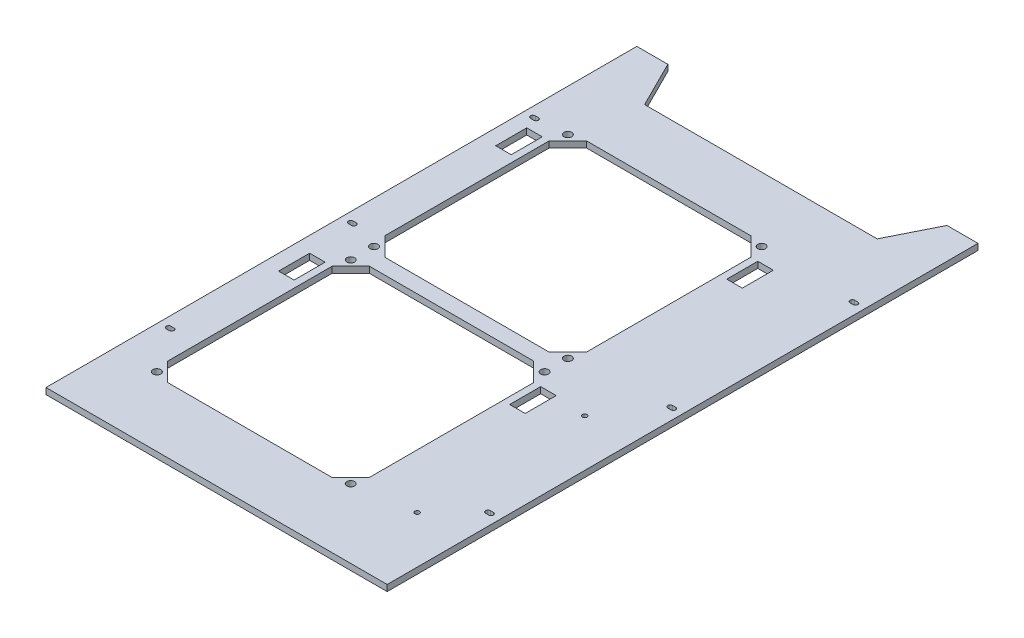
SolidWorks part; units mm, degrees
ref_plane "前基準面" through (0, 0, 0) normal (0, 0, 1) x (1, 0, 0)
ref_plane "上基準面" through (0, 0, 0) normal (0, 1, 0) x (1, 0, 0)
ref_plane "右基準面" through (0, 0, 0) normal (1, 0, 0) x (0, 0, -1)
sketch "草圖1" plane through (0, 0, 0) normal (0, 1, 0) x (1, 0, 0)
  line L1 (-110, 190.5) -> (110, 190.5)
  line L2 (-110, 190.5) -> (-110, -190.5)
  line L3 (-110, -190.5) -> (110, -190.5)
  line L4 (110, 190.5) -> (110, -190.5)
  line L5 (-110, 190.5) -> (110, -190.5) construction
  line L6 (-110, -190.5) -> (110, 190.5) construction
  point P0 (0, 0)
  dimension "D1" = 220
  dimension "D2" = 381
extrude "填料-伸長1" add sketch "草圖1" along normal blind 4
sketch "草圖4" plane through (0, 4, 0) normal (0, 1, 0) x (1, 0, 0)
  line L0 (-110, -190.5) -> (110, -190.5) construction
  line L1 (-103, -117.5) -> (-93, -117.5) construction
  line L2 (-110, 190.5) -> (-110, -190.5) construction
  line L4 (103, -117.5) -> (93, -117.5) construction
  line L5 (103, -117.5) -> (103, 0) construction
  line L6 (110, -190.5) -> (110, 190.5) construction
  line L7 (-103, -117.5) -> (-103, 0) construction
  point P0 (-103, -117.5)
  point P15 (103, -117.5)
  point P21 (93, -117.5)
  point P22 (93, 0)
  point P23 (93, 117.5)
  point P24 (103, 0)
  point P25 (103, 117.5)
  point P26 (-93, -117.5)
  point P27 (-93, 0)
  point P28 (-93, 117.5)
  point P29 (-103, 0)
  point P30 (-103, 117.5)
  dimension "D3" = 2
  dimension "D4" = 3
  dimension "D5" = 7
  dimension "D6" = 10
  dimension "D9" = 3
  dimension "D10" = 10
  dimension "D11" = 7
  dimension "D12" = 117.5
  dimension "D2" = 73
  dimension "D13" = 117.5
  dimension "D7" = 73
  dimension "D8" = 2
hole_wizard "Ø3.0mm 定位孔3" positions "3D草圖6" profile "草圖15" hole size "Ø3.0" standard "GB" end condition through all
sketch3d "3D草圖6"
  point P0 (-103, 4, -117.5)
  point P3 (103, 4, -117.5)
  point P6 (103, 4, 0)
  point P9 (-103, 4, 0)
  point P12 (103, 4, 117.5)
  point P15 (-103, 4, 117.5)
sketch "草圖15" plane through (-103, 4, -117.5) normal (1, 0, 0) x (0, 0, 1)
  line L0 (0, 0) -> (0, 4)
  line L1 (0, 4) -> (1.5, 4)
  line L2 (1.5, 4) -> (1.5, 0)
  line L5 (1.5, 0) -> (0, 0)
  line L11 (0, -6.35) -> (0, 107.95) construction
  dimension "貫穿孔直徑" = 3
  dimension "貫穿孔深度" = 4
sketch "草圖6" plane through (0, 4, 0) normal (0, 1, 0) x (1, 0, 0)
  line L0 (-83, 57) -> (-83, 127) construction
  line L1 (-85, 57) -> (-85, 127)
  line L2 (-81, 57) -> (-81, 127)
  line L3 (59, -50.5) -> (49, -50.5)
  line L4 (110, 190.5) -> (-110, 190.5) construction
  line L5 (-110, 190.5) -> (-110, -190.5) construction
  line L6 (42, 57) -> (42, 127) construction
  line L7 (40, 57) -> (40, 127)
  line L8 (44, 57) -> (44, 127)
  line L9 (42, -48.5) -> (42, 21.5) construction
  line L10 (40, -48.5) -> (40, 21.5)
  line L11 (44, -48.5) -> (44, 21.5)
  line L12 (42, -154) -> (42, -84) construction
  line L13 (40, -154) -> (40, -84)
  line L14 (44, -154) -> (44, -84)
  line L15 (-83, -48.5) -> (-83, 21.5) construction
  line L16 (-85, -48.5) -> (-85, 21.5)
  line L17 (-81, -48.5) -> (-81, 21.5)
  line L18 (-83, -154) -> (-83, -84) construction
  line L19 (-85, -154) -> (-85, -84)
  line L20 (-81, -154) -> (-81, -84)
  line L21 (-83, 57) -> (42, 57) construction
  line L22 (-83, 57) -> (-83, -48.5) construction
  line L47 (-20.5, 61) -> (-20.5, 177.5) construction
  line L48 (-20.5, 61) -> (-20.5, -135.5) construction
  line L53 (-100, -30.5) -> (-90, -30.5)
  line L54 (-100, -30.5) -> (-100, -50.5)
  line L55 (-100, -50.5) -> (-90, -50.5)
  line L56 (-90, -30.5) -> (-90, -50.5)
  line L57 (49, -30.5) -> (49, -50.5)
  line L58 (59, -30.5) -> (49, -30.5)
  line L59 (59, -30.5) -> (59, -50.5)
  line L60 (-110, -190.5) -> (110, -190.5) construction
  line L61 (-100, 109.5) -> (-100, 89.5)
  line L62 (-100, 109.5) -> (-90, 109.5)
  line L63 (-90, 109.5) -> (-90, 89.5)
  line L64 (-100, 89.5) -> (-90, 89.5)
  line L65 (59, 89.5) -> (49, 89.5)
  line L66 (49, 109.5) -> (49, 89.5)
  line L67 (59, 109.5) -> (49, 109.5)
  line L68 (59, 109.5) -> (59, 89.5)
  line L69 (-100, -30.5) -> (-100, 109.5) construction
  arc A0 (-85, 57) -> (-81, 57) centre (-83, 57) ccw
  arc A1 (-81, 127) -> (-85, 127) centre (-83, 127) ccw
  arc A2 (40, 57) -> (44, 57) centre (42, 57) ccw
  arc A3 (44, 127) -> (40, 127) centre (42, 127) ccw
  arc A4 (40, -48.5) -> (44, -48.5) centre (42, -48.5) ccw
  arc A5 (44, 21.5) -> (40, 21.5) centre (42, 21.5) ccw
  arc A6 (40, -154) -> (44, -154) centre (42, -154) ccw
  arc A7 (44, -84) -> (40, -84) centre (42, -84) ccw
  arc A8 (-85, -48.5) -> (-81, -48.5) centre (-83, -48.5) ccw
  arc A9 (-81, 21.5) -> (-85, 21.5) centre (-83, 21.5) ccw
  arc A10 (-85, -154) -> (-81, -154) centre (-83, -154) ccw
  arc A11 (-81, -84) -> (-85, -84) centre (-83, -84) ccw
  point P2 (-83, 92)
  point P15 (42, 92)
  point P22 (42, -13.5)
  point P29 (42, -119)
  point P36 (-83, -13.5)
  point P43 (-83, -119)
  dimension "D2" = 2
  dimension "D1" = 90
  dimension "D3" = 27
  dimension "D4" = 70
  dimension "D5" = 317.5
  dimension "D8" = 125
  dimension "D9" = 105.5
  dimension "D10" = 89.5
  dimension "D11" = 10
  dimension "D12" = 116.5
  dimension "D13" = 20
  dimension "D14" = 10
  dimension "D15" = 196.5
  dimension "D16" = 13
  dimension "D18" = 140
  dimension "D6" = 2
  dimension "D7" = 3
  dimension "D17" = 2
extrude "除料-伸長1" cut sketch "草圖6" against normal through all contours L61 L64 L63 L62 | L68 L67 L66 L65 | L59 L58 L57 L3 | L56 L53 L54 L55 region at (54, 4, 40.5) region at (-95, 4, 40.5) region at (-95, 4, -99.5) region at (54, 4, -99.5)
sketch "草圖18" plane through (0, 4, 0) normal (0, 1, 0) x (1, 0, 0)
  line L0 (-83, 119) -> (42, 119) construction
  line L1 (-83, 119) -> (-83, -6) construction
  line L2 (-83, -21) -> (42, -21) construction
  line L3 (-83, -21) -> (-83, -146) construction
  line L6 (-110, 190.5) -> (-110, -190.5) construction
  line L8 (-110, -190.5) -> (110, -190.5) construction
  point P0 (-83, 119)
  point P1 (-83, -21)
  point P4 (42, 119)
  point P5 (42, -6)
  point P6 (-83, -6)
  point P11 (42, -21)
  point P12 (42, -146)
  point P13 (-83, -146)
  dimension "D3" = 125
  dimension "D4" = 125
  dimension "D7" = 125
  dimension "D8" = 125
  dimension "D9" = 15
  dimension "D10" = 27
  dimension "D11" = 309.5
  dimension "D1" = 2
  dimension "D2" = 2
  dimension "D5" = 2
  dimension "D6" = 2
sketch "草圖19" plane through (0, 4, 0) normal (0, 1, 0) x (1, 0, 0)
  line L0 (-83, 119) -> (42, 119) construction
  line L3 (-83, 119) -> (-83, -6) construction
  line L6 (-83, -146) -> (42, -146) construction
  line L9 (-83, -146) -> (-83, -21) construction
  circle A16 centre (-83, 119) radius 2.5
  circle A17 centre (42, 119) radius 2.5
  circle A18 centre (42, -6) radius 2.5
  circle A19 centre (-83, -6) radius 2.5
  circle A20 centre (-83, -146) radius 2.5
  circle A21 centre (42, -146) radius 2.5
  circle A22 centre (42, -21) radius 2.5
  circle A23 centre (-83, -21) radius 2.5
  dimension "D1" = 5
  dimension "D7" = 2
  dimension "D6" = 5
  dimension "D2" = 2
  dimension "D5" = 125
  dimension "D8" = 2
  dimension "D4" = 125
  dimension "D9" = 125
  dimension "D10" = 125
  dimension "D3" = 2
extrude "除料-伸長5" cut sketch "草圖19" against normal through all contours A17 | A19 | A22 | A21 | A20 | A16 | A18 | A23 region at (42, 4, -119) region at (-83, 4, 6) region at (-83, 4, 146) region at (42, 4, 146) region at (42, 4, 21)
sketch "草圖20" plane through (0, 4, 0) normal (0, 1, 0) x (1, 0, 0)
  line L0 (-85.5, 109.5) -> (-73.5, 121.5)
  line L1 (-73.5, -8.5) -> (32.5, -8.5)
  line L2 (-85.5, 3.5) -> (-85.5, 109.5)
  line L3 (-73.5, 121.5) -> (32.5, 121.5)
  line L4 (44.5, 3.5) -> (44.5, 109.5)
  line L5 (-85.5, -8.5) -> (44.5, 121.5) construction
  line L6 (-85.5, 121.5) -> (44.5, -8.5) construction
  line L7 (-73.5, -18.5) -> (32.5, -18.5)
  line L8 (-85.5, -30.5) -> (-85.5, -136.5)
  line L9 (-73.5, -148.5) -> (32.5, -148.5)
  line L10 (44.5, -30.5) -> (44.5, -136.5)
  line L11 (-85.5, -18.5) -> (44.5, -148.5) construction
  line L12 (-85.5, -148.5) -> (44.5, -18.5) construction
  line L13 (32.5, 121.5) -> (44.5, 109.5)
  line L14 (32.5, -8.5) -> (44.5, 3.5)
  line L15 (-85.5, 3.5) -> (-73.5, -8.5)
  line L16 (-85.5, -30.5) -> (-73.5, -18.5)
  line L17 (32.5, -18.5) -> (44.5, -30.5)
  line L18 (32.5, -148.5) -> (44.5, -136.5)
  line L19 (-85.5, -136.5) -> (-73.5, -148.5)
  circle A0 centre (-83, 119) radius 2.5 construction
  circle A1 centre (42, 119) radius 2.5 construction
  circle A2 centre (42, -6) radius 2.5 construction
  circle A3 centre (-83, -21) radius 2.5 construction
  circle A4 centre (42, -21) radius 2.5 construction
  circle A5 centre (42, -146) radius 2.5 construction
  point P0 (-20.5, 56.5)
  point P11 (-20.5, -83.5)
extrude "除料-伸長6" cut sketch "草圖20" against normal through all
sketch "草圖12" plane through (0, 4, 0) normal (0, 1, 0) x (1, 0, 0)
  line L0 (110, -190.5) -> (110, 190.5) construction
  line L1 (-110, -190.5) -> (110, -190.5) construction
  line L2 (79.5, -140.62) -> (79.5, -32.62) construction
  point P0 (79.5, -140.62)
  point P6 (79.5, -32.62)
  dimension "D1" = 30.5
  dimension "D2" = 49.88
  dimension "D4" = 108
  dimension "D3" = 2
hole_wizard "Ø3.0mm 定位孔2" positions "3D草圖4" profile "草圖13" hole size "Ø3.0" standard "GB" end condition through all
sketch3d "3D草圖4"
  point P0 (79.5, 4, 32.62)
  point P3 (79.5, 4, 140.62)
sketch "草圖13" plane through (79.5, 4, 32.62) normal (1, 0, 0) x (0, 0, 1)
  line L0 (0, 0) -> (0, 4)
  line L1 (0, 4) -> (1.5, 4)
  line L2 (1.5, 4) -> (1.5, 0)
  line L5 (1.5, 0) -> (0, 0)
  line L11 (0, -6.35) -> (0, 107.95) construction
  dimension "貫穿孔直徑" = 3
  dimension "貫穿孔深度" = 4
sketch "草圖16" plane through (0, 4, 0) normal (0, 1, 0) x (1, 0, 0)
  line L0 (-90, 190.5) -> (90, 190.5)
  line L1 (110, 190.5) -> (-110, 190.5) construction
  line L2 (-75, 160.5) -> (75, 160.5)
  line L3 (-90, 190.5) -> (-110, 190.5) construction
  line L4 (90, 190.5) -> (110, 190.5) construction
  line L5 (75, 160.5) -> (110, 160.5) construction
  line L6 (110, -190.5) -> (110, 190.5) construction
  line L7 (-75, 160.5) -> (-110, 160.5) construction
  line L8 (-110, 190.5) -> (-110, -190.5) construction
  line L9 (-90, 190.5) -> (-75, 160.5)
  line L10 (90, 190.5) -> (75, 160.5)
  dimension "D1" = 30
  dimension "D2" = 180
  dimension "D3" = 150
extrude "除料-伸長3" cut sketch "草圖16" against normal through all
sketch "草圖17" plane through (0, 4, 0) normal (0, 1, 0) x (1, 0, 0)
  line L0 (-104, 117.5) -> (-102, 117.5) construction
  line L1 (-104, 119) -> (-102, 119)
  line L2 (-104, 116) -> (-102, 116)
  line L3 (102, 117.5) -> (104, 117.5) construction
  line L4 (102, 119) -> (104, 119)
  line L5 (102, 116) -> (104, 116)
  line L6 (102, 0) -> (104, 0) construction
  line L7 (102, 1.5) -> (104, 1.5)
  line L8 (102, -1.5) -> (104, -1.5)
  line L9 (102, -117.5) -> (104, -117.5) construction
  line L10 (102, -116) -> (104, -116)
  line L11 (102, -119) -> (104, -119)
  line L12 (-104, 0) -> (-102, 0) construction
  line L13 (-104, 1.5) -> (-102, 1.5)
  line L14 (-104, -1.5) -> (-102, -1.5)
  line L15 (-104, -117.5) -> (-102, -117.5) construction
  line L16 (-104, -116) -> (-102, -116)
  line L17 (-104, -119) -> (-102, -119)
  line L18 (-104, 117.5) -> (102, 117.5) construction
  line L19 (-104, 117.5) -> (-104, 0) construction
  arc A0 (-104, 119) -> (-104, 116) centre (-104, 117.5) ccw
  arc A1 (-102, 116) -> (-102, 119) centre (-102, 117.5) ccw
  arc A2 (102, 119) -> (102, 116) centre (102, 117.5) ccw
  arc A3 (104, 116) -> (104, 119) centre (104, 117.5) ccw
  arc A4 (102, 1.5) -> (102, -1.5) centre (102, 0) ccw
  arc A5 (104, -1.5) -> (104, 1.5) centre (104, 0) ccw
  arc A6 (102, -116) -> (102, -119) centre (102, -117.5) ccw
  arc A7 (104, -119) -> (104, -116) centre (104, -117.5) ccw
  arc A8 (-104, 1.5) -> (-104, -1.5) centre (-104, 0) ccw
  arc A9 (-102, -1.5) -> (-102, 1.5) centre (-102, 0) ccw
  arc A10 (-104, -116) -> (-104, -119) centre (-104, -117.5) ccw
  arc A11 (-102, -119) -> (-102, -116) centre (-102, -117.5) ccw
  point P2 (-103, 117.5)
  point P13 (103, 117.5)
  point P20 (103, 0)
  point P27 (103, -117.5)
  point P34 (-103, 0)
  point P41 (-103, -117.5)
  dimension "D2" = 1.5
  dimension "D1" = 2
  dimension "D5" = 206
  dimension "D6" = 117.5
  dimension "D3" = 2
  dimension "D4" = 3
extrude "除料-伸長4" cut sketch "草圖17" against normal through all
